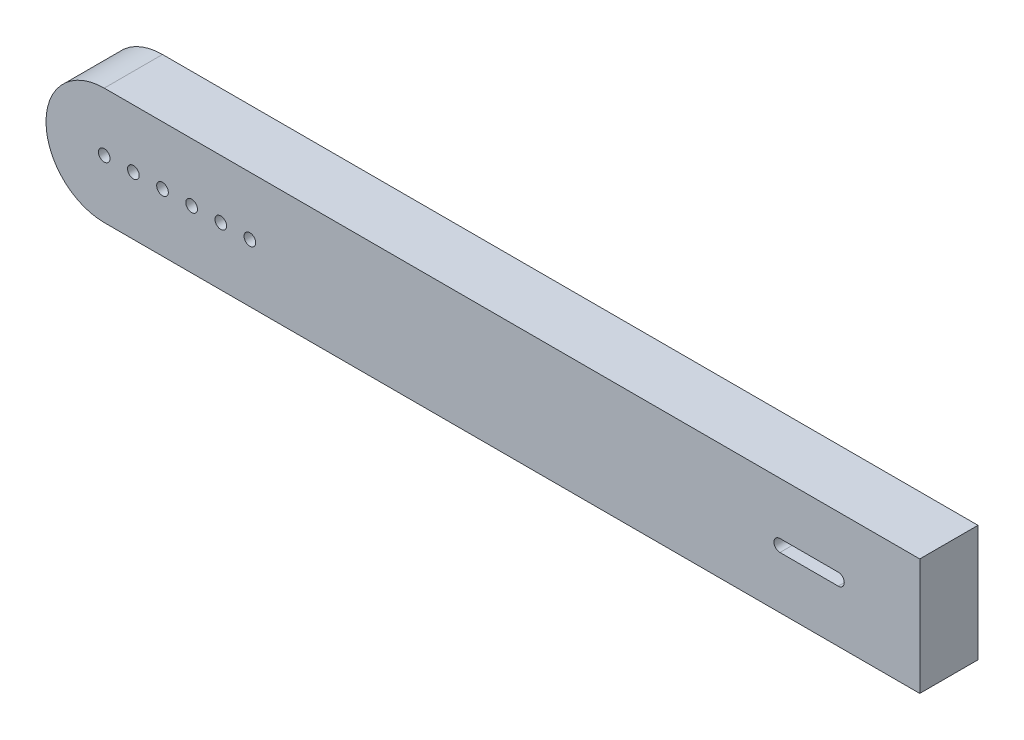
SolidWorks part; units mm, degrees
ref_plane "Front Plane" through (0, 0, 0) normal (0, 0, 1) x (1, 0, 0)
ref_plane "Top Plane" through (0, 0, 0) normal (0, 1, 0) x (1, 0, 0)
ref_plane "Right Plane" through (0, 0, 0) normal (1, 0, 0) x (0, 0, -1)
sketch "Sketch1" plane through (0, 0, 0) normal (0, 0, 1) x (1, 0, 0)
  line L0 (-24.9751, -0.4993) -> (-25.7148, -0.4993)
  line L1 (-40.9548, -6.8493) -> (47.9452, -6.8493)
  line L3 (-40.9548, 5.8507) -> (47.9452, 5.8507)
  line L4 (47.9452, -6.8493) -> (47.9452, 5.8507)
  line L5 (-40.9548, -6.8493) -> (-0.1509, -0.0252) construction
  line L6 (-40.9548, 5.8507) -> (47.9452, -6.8493) construction
  line L8 (-24.4448, -0.4993) -> (-25.7148, -0.4993)
  line L9 (39.6902, -0.4993) -> (38.4202, -0.4993)
  line L10 (-41.5898, -0.4998) -> (-40.3198, -0.4988)
  line L11 (-35.2398, -0.4993) -> (-33.9698, -0.4993)
  line L12 (-37.1448, -0.4993) -> (-37.1448, -0.4992)
  line L13 (-33.9698, -0.4993) -> (-35.2398, -0.4993)
  line L14 (-32.0648, -0.4993) -> (-30.7948, -0.4993)
  line L15 (-30.7948, -0.4993) -> (-32.0648, -0.4993)
  line L16 (-28.8898, -0.4993) -> (-27.6198, -0.4993)
  line L17 (-28.8898, -0.4993) -> (-27.6198, -0.4993)
  line L18 (-27.6198, -0.4993) -> (-28.8898, -0.4993)
  line L19 (-25.7148, -0.4993) -> (-24.4448, -0.4993)
  line L20 (-25.7148, -0.4993) -> (-24.4448, -0.4993)
  line L21 (-24.4448, -0.4993) -> (-25.7148, -0.4993)
  line L22 (39.6902, -0.4993) -> (38.4202, -0.4993)
  line L23 (39.6902, -0.4993) -> (38.4202, -0.4993)
  line L24 (33.3402, -0.4993) -> (32.0702, -0.4993)
  line L25 (33.3402, -0.4993) -> (32.0702, -0.4993)
  line L26 (33.3402, -0.4993) -> (32.0702, -0.4993)
  line L27 (36.5152, -0.4993) -> (35.2452, -0.4993)
  line L28 (36.5152, -0.4993) -> (35.2452, -0.4993)
  line L29 (36.5152, -0.4993) -> (35.2452, -0.4993)
  line L30 (-27.6198, -0.4993) -> (-32.0648, -0.4993)
  line L31 (-27.6198, -0.4993) -> (-28.8898, -0.4993)
  line L32 (-33.9698, -0.4993) -> (-35.2398, -0.4993)
  circle A0 centre (-40.9548, -0.4993) radius 0.635
  circle A1 centre (-37.7798, -0.4993) radius 0.635
  circle A2 centre (-34.6048, -0.4993) radius 0.635
  circle A3 centre (-31.4298, -0.4993) radius 0.635
  circle A4 centre (32.7052, -0.4993) radius 0.635
  circle A5 centre (-28.2548, -0.4993) radius 0.635
  circle A6 centre (-25.0798, -0.4993) radius 0.635
  circle A7 centre (35.8802, -0.4993) radius 0.635
  circle A8 centre (39.0552, -0.4993) radius 0.635
  arc A9 (-39.1768, 5.5967) -> (-38.8886, -6.5038) centre (-40.9548, -0.4993) ccw
  point P0 (0, 0)
  dimension "D1" = 1.27
  dimension "D2" = 1.27
  dimension "D3" = 3.175
  dimension "D5" = 1.27
  dimension "D11" = 6.35
  dimension "D4" = 2
  dimension "D6" = 2
  dimension "D8" = 88.9
  dimension "D9" = 8.89
  dimension "D10" = 12.7
  dimension "D7" = 3
extrude "Boss-Extrude3" add sketch "Sketch1" along normal blind 6.35 contours A4 L4 L3 A0 A1 A2 A3 | A4 A3 A2 A1 A0 L1 L4 region at (1.0975, -0.4993, 0)
sketch "Sketch2" plane through (0, 0, 6.35) normal (0, 0, 1) x (1, 0, 0)
  line L3 (32.7052, -1.1597) -> (39.0552, -1.1597)
  line L4 (32.7052, 0.1611) -> (39.0552, 0.1611)
  arc A0 (32.7052, 0.1611) -> (32.7052, -1.1597) centre (32.7052, -0.4993) ccw
  arc A1 (39.0552, -1.1597) -> (39.0552, 0.1611) centre (39.0552, -0.4993) ccw
  circle A3 centre (-25.0798, -0.4993) radius 0.635 construction
  dimension "D1" = 1.3208
extrude "Cut-Extrude2" cut sketch "Sketch2" against normal blind 25.4 contours L3 A1 L4 A0
